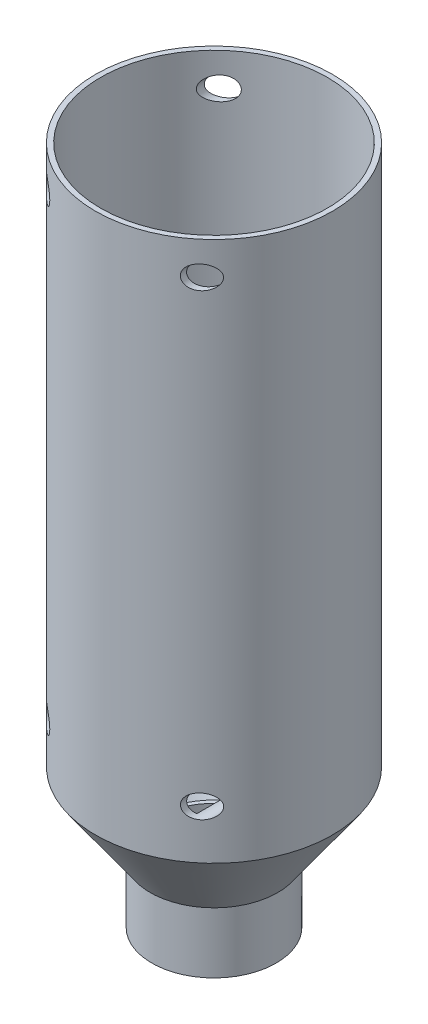
SolidWorks part; units mm, degrees
ref_plane "Front Plane" through (0, 0, 0) normal (0, 0, 1) x (1, 0, 0)
ref_plane "Top Plane" through (0, 0, 0) normal (0, 1, 0) x (1, 0, 0)
ref_plane "Right Plane" through (0, 0, 0) normal (1, 0, 0) x (0, 0, -1)
sketch "Sketch1" plane through (0, 0, 0) normal (0, 0, 1) x (1, 0, 0)
  line L0 (-12.065, 0) -> (-12.065, 12)
  line L1 (-12.065, 12) -> (-12.369, 12)
  line L2 (-12.369, 12) -> (-23, 27)
  line L3 (-23, 27) -> (-23, 127.3184)
  line L4 (-23, 127.3184) -> (-22, 127.3184)
  line L5 (-22, 127.3184) -> (-22, 27.3184)
  line L6 (-22, 27.3184) -> (-11.852, 13)
  line L7 (-11.852, 13) -> (-11.065, 13)
  line L8 (-11.065, 13) -> (-11.065, 0)
  line L9 (-11.065, 0) -> (-12.065, 0)
  line L10 (0, 0) -> (0, 43.0418) construction
  dimension "D1" = 1
  dimension "D2" = 12.065
  dimension "D3" = 12.369
  dimension "D4" = 1
  dimension "D5" = 1
  dimension "D6" = 1
  dimension "D7" = 15
  dimension "D8" = 22
  dimension "D9" = 12
  dimension "D10" = 0
  dimension "D11" = 100
revolve "Revolve1" add sketch "Sketch1" angle 360 about L10
sketch "Sketch4" plane through (0, 127.3184, 0) normal (0, 1, 0) x (1, 0, 0)
  line L1 (22.9787, -0.9892) -> (-22.9919, -0.9892)
  line L2 (22.9787, -0.9892) -> (22.9787, 0.6108)
  line L3 (22.9787, 0.6108) -> (-22.9919, 0.6108)
  line L4 (-22.9919, -0.9892) -> (-22.9919, 0.6108)
  circle A0 centre (0, 0) radius 23 construction
sketch "Sketch5" plane through (0, 0, 0.9892) normal (0, 0, 1) x (1, 0, 0)
  line L1 (-22, 127.3184) -> (-22, 27.3184) construction
  line L2 (-22, 38.3873) -> (-22, 27.3184)
  line L4 (-13.8091, 33.1759) -> (-13.8091, 38.3873)
  line L8 (-13.5091, 28.9084) -> (-13.5091, 34.6084) construction
  line L9 (-22, 27.3184) -> (-13.8091, 33.1759)
  line L10 (0, 37.788) -> (0, 30.7839) construction
  line L11 (0, 0) -> (0, 43.0418) construction
  line L12 (22, 38.3873) -> (22, 27.3184)
  line L14 (13.8091, 33.1759) -> (13.8091, 38.3873)
  line L15 (22, 27.3184) -> (13.8091, 33.1759)
  line L16 (13.8091, 38.3873) -> (22, 46.5782)
  line L17 (22, 46.5782) -> (22, 38.3873)
  line L18 (-13.8091, 38.3873) -> (-22, 46.5782)
  line L19 (-22, 46.5782) -> (-22, 38.3873)
  circle A0 centre (-14.9291, 36.5134) radius 0.925
  circle A1 centre (14.9291, 36.5134) radius 0.925
  dimension "D1" = 0.3
extrude "Boss-Extrude1" add sketch "Sketch5" along normal up to next from offset 0.2
sketch "Sketch7" plane through (0, 0, -0.6108) normal (0, 0, -1) x (-1, 0, 0)
  line L0 (-22, 27.3184) -> (-13.8091, 33.1759)
  line L1 (-13.8091, 33.1759) -> (-13.8091, 38.3873)
  line L3 (-22, 38.3873) -> (-22, 27.3184)
  line L4 (0, 37.788) -> (0, 30.7839) construction
  line L6 (13.8091, 33.1759) -> (13.8091, 38.3873)
  line L7 (22, 27.3184) -> (13.8091, 33.1759)
  line L8 (22, 38.3873) -> (22, 27.3184)
  line L9 (-13.8091, 38.3873) -> (-22, 46.5782)
  line L10 (-22, 46.5782) -> (-22, 38.3873)
  line L11 (13.8091, 38.3873) -> (22, 46.5782)
  line L12 (22, 46.5782) -> (22, 38.3873)
  circle A0 centre (-14.9291, 36.5134) radius 0.925
  circle A1 centre (14.9291, 36.5134) radius 0.925
  point P15 (14.9291, 36.5134)
extrude "Boss-Extrude3" add sketch "Sketch7" along normal up to next from offset 0.3 separate body
sketch "Sketch8" plane through (0, 0, -0.6108) normal (0, 0, -1) x (-1, 0, 0)
  line L1 (-23, 27) -> (23, 27) construction
  circle A0 centre (-14.9159, 125.4134) radius 0.925
  circle A1 centre (14.9291, 125.4134) radius 0.925
  circle A2 centre (-14.9291, 36.5134) radius 0.925
  circle A3 centre (14.9291, 36.5134) radius 0.925
  dimension "D1" = 88.9
  dimension "D2" = 88.9
  dimension "D3" = 29.845
  dimension "D4" = 29.8582
  dimension "D5" = 9.5134
  dimension "D6" = 9.5134
extrude "Cut-Extrude1" cut sketch "Sketch8" against normal through all both and the other way through all
sketch "Sketch13" plane through (0, 127.3184, 0) normal (0, 1, 0) x (1, 0, 0)
  circle A0 centre (0, 0) radius 22
  circle A1 centre (0, 0) radius 23
extrude "Boss-Extrude7" add sketch "Sketch13" along normal blind 4.5
ref_plane "Plane1" through (0, 0, -23) normal (0, 0, -1) x (-1, 0, 0)
sketch "Sketch14" plane through (0, 0, -23) normal (0, 0, -1) x (-1, 0, 0)
  circle A0 centre (-14.9159, 125.4134) radius 2.25
  circle A1 centre (14.9291, 125.4134) radius 2.25
  circle A2 centre (14.9291, 36.5134) radius 2.25
  circle A3 centre (-14.9291, 36.5134) radius 2.25
  dimension "D1" = 4.5
  dimension "D2" = 4.5
  dimension "D3" = 4.5
  dimension "D4" = 4.5
extrude "Cut-Extrude2" cut sketch "Sketch14" against normal blind 14
ref_plane "Plane2" through (0, 0, 23) normal (0, 0, 1) x (1, 0, 0)
sketch "Sketch15" plane through (0, 0, 23) normal (0, 0, 1) x (1, 0, 0)
  circle A0 centre (14.9159, 125.4134) radius 2.25
  circle A1 centre (-14.9291, 125.4134) radius 2.25
  circle A2 centre (14.9291, 36.5134) radius 2.25
  circle A3 centre (-14.9291, 36.5134) radius 2.25
  dimension "D1" = 4.5
  dimension "D2" = 4.5
  dimension "D3" = 4.5
  dimension "D4" = 4.5
extrude "Cut-Extrude3" cut sketch "Sketch15" against normal blind 14
